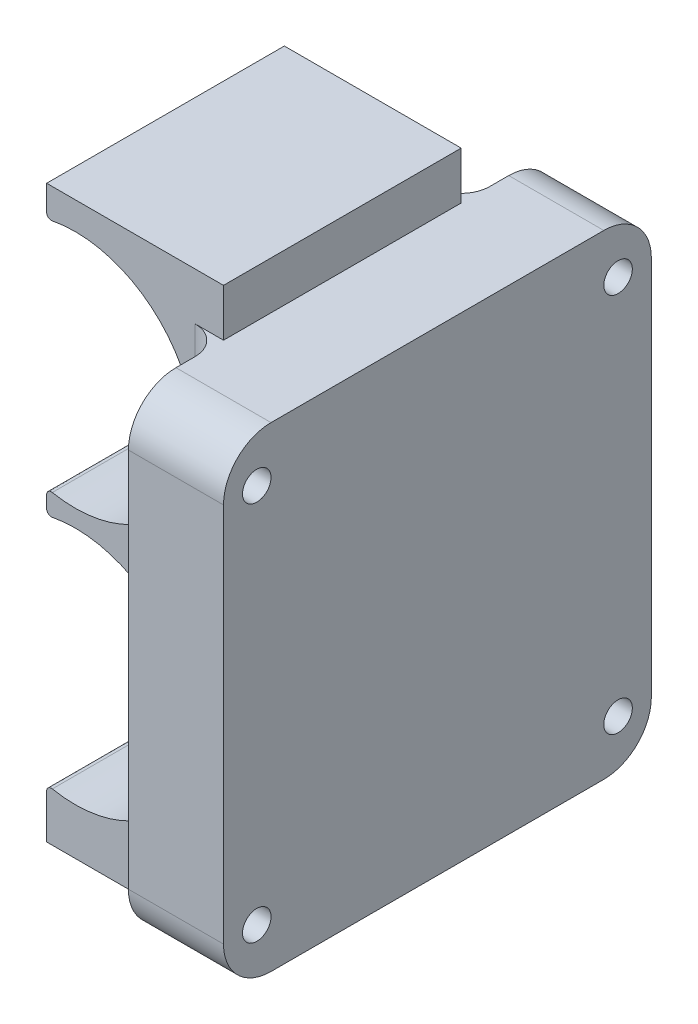
SolidWorks part; units mm, degrees
ref_plane "Front Plane" through (0, 0, 0) normal (0, 0, 1) x (1, 0, 0)
ref_plane "Top Plane" through (0, 0, 0) normal (0, 1, 0) x (1, 0, 0)
ref_plane "Right Plane" through (0, 0, 0) normal (1, 0, 0) x (0, 0, -1)
sketch "Sketch1" plane through (0, 0, 0) normal (0, 0, 1) x (1, 0, 0)
  line L0 (0, 0) -> (0, 58)
  line L1 (0, 58) -> (-18.6, 58)
  line L2 (-18.6, 58) -> (-18.6, 0)
  line L3 (-18.6, 0) -> (0, 0)
  line L4 (-15.6, 0) -> (-15.6, 58) construction
  line L5 (-15.6, 29) -> (0, 29) construction
  circle A0 centre (-15.6, 15.5) radius 12.6
  circle A1 centre (-15.6, 42.5) radius 12.6
  point P9 (-28.2, 15.5)
  point P13 (-3, 15.5)
  point P15 (-16.6, 4.4408)
  point P18 (-15.9021, 2.9036)
  dimension "D1" = 27
  dimension "25.2" = 25.2
  dimension "D2" = 3
  dimension "D3" = 3
  dimension "D4" = 58
extrude "Boss-Extrude1" add sketch "Sketch1" along normal blind 25 contours L2 A1 A0 L3 L0 L1
sketch "Sketch2" plane through (0, 0, 0) normal (0, -1, 0) x (1, 0, 0)
  line L4 (-18.6, 0) -> (0, 0)
  line L5 (0, 0) -> (0, 25)
  line L6 (0, 25) -> (-18.6, 25)
  line L7 (-18.6, 25) -> (-18.6, 0)
  line L8 (-18.6, 0) -> (0, 0)
  line L9 (0, 0) -> (0, 25)
  line L10 (0, 25) -> (-18.6, 25)
  line L11 (-18.6, 25) -> (-18.6, 0)
  dimension "D1" = 0
extrude "Boss-Extrude2" add sketch "Sketch2" along normal blind 2
fillet "Fillet1" radius 0.5 4 edges at (-18.6, 3.2624, 12.5) (-18.6, 27.7376, 12.5) (-18.6, 30.2624, 12.5) (-18.6, 54.7376, 12.5)
sketch "Sketch3" plane through (0, 0, 0) normal (1, 0, 0) x (0, 0, -1)
  line L0 (-25, -2) -> (-25, 58) construction
  line L1 (-25, 53) -> (-35, 53)
  line L2 (-25, 53) -> (-25, 3) construction
  line L3 (-25, 3) -> (-35, 3)
  line L4 (-35, 53) -> (-35, 3)
  line L5 (0, -2) -> (-25, -2) construction
  line L6 (-25, 58) -> (0, 58) construction
  line L7 (-12.5, -2) -> (-12.5, 58) construction
  line L8 (0, 3) -> (10, 3)
  line L9 (-25, 53) -> (0, 53)
  line L10 (-25, 53) -> (-25, 3) construction
  line L11 (-25, 3) -> (0, 3)
  line L12 (-12.5, 53) -> (-12.5, 3)
  line L13 (10, 53) -> (10, 3)
  line L14 (0, 53) -> (10, 53)
  line M9 (0, -2) -> (0, 58)
  line M11 (-25, 58) -> (-25, -2)
  dimension "D1" = 5
  dimension "D2" = 5
  dimension "D3" = 10
extrude "Boss-Extrude3" add sketch "Sketch3" along normal blind 10 contours L12 L9 L11 M11 | L9 L12 L11 M9 | L14 L8 L13 M9 | L1 L4 L3 M11
fillet "Fillet2" radius 3 2 edges at (0, 28, 0) (0, 28, 25)
sketch "Sketch4" plane through (0, 0, 0) normal (-1, 0, 0) x (0, 0, 1)
  line L0 (-6.5, 53) -> (-6.5, 3) construction
  line L1 (-3, 53) -> (-10, 53) construction
  line L2 (-3, 3) -> (-10, 3) construction
  line L3 (12.5, 2.6408) -> (12.5, 55.3592) construction
  line L4 (25, 2.6408) -> (0, 2.6408) construction
  line L5 (0, 55.3592) -> (25, 55.3592) construction
  circle A0 centre (-6.5, 48) radius 1.5
  circle A1 centre (-6.5, 8) radius 1.5
  circle A2 centre (31.5, 8) radius 1.5
  circle A3 centre (31.5, 48) radius 1.5
  dimension "D1" = 3
  dimension "D2" = 5
  dimension "D3" = 5
extrude "Cut-Extrude1" cut sketch "Sketch4" against normal through all
fillet "Fillet3" radius 5 4 edges at (5, 3, 35) (5, 53, -10) (5, 3, -10) (5, 53, 35)
